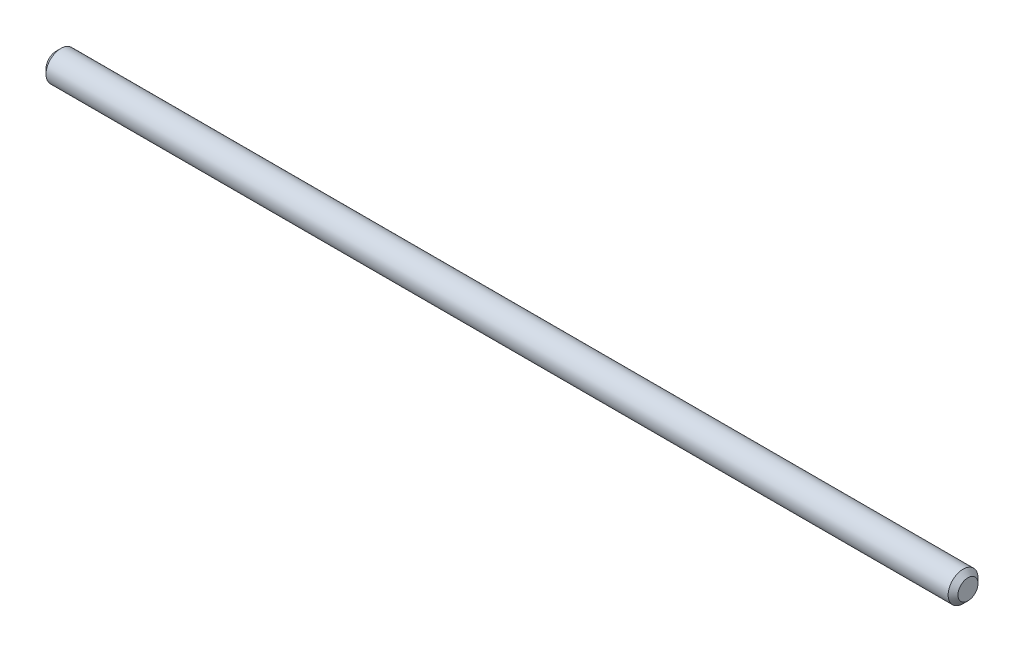
SolidWorks part; units mm, degrees
material "Plain Carbon Steel"
ref_plane "Front Plane" through (0, 0, 0) normal (0, 0, 1) x (1, 0, 0)
ref_plane "Top Plane" through (0, 0, 0) normal (0, 1, 0) x (1, 0, 0)
ref_plane "Right Plane" through (0, 0, 0) normal (1, 0, 0) x (0, 0, -1)
sketch "Sketch1" plane through (0, 0, 0) normal (0, 0, 1) x (1, 0, 0)
  line L0 (-73.66, 0) -> (73.66, 0) construction
  line L1 (73.66, 2.413) -> (73.66, -2.413) construction
  line L2 (-73.66, 2.413) -> (-73.66, -2.413) construction
  line L3 (73.66, 2.413) -> (4.8683, 2.413) construction
  point P6 (69.9558, -2.413)
  point P9 (-64.008, 0)
  point P10 (64.008, 0)
  point P11 (-38.608, 0)
  point P12 (38.608, 0)
  dimension "D1" = 3.7042
  dimension "D2" = 9.652
  dimension "D3" = 9.652
  dimension "D4" = 25.4
  dimension "D5" = 25.4
sketch "Sketch2" plane through (0, 0, 0) normal (1, 0, 0) x (0, 0, -1)
  circle A0 centre (0, 0) radius 2.413
extrude "Boss-Extrude1" add sketch "Sketch2" against normal up to vertex (73.66 mm away) and the other way up to vertex (73.66 mm away) up to point (-73.66, 0, 0) other way up to point (73.66, 0, 0)
chamfer "Chamfer1" distance 0.7938 angle 45 2 edges at (-73.66, 0, -2.413) (73.66, 0, -2.413)
sketch "Drawing1" plane through (0, 0, 0) normal (1, 0, 0) x (0, 0, -1)
  circle A0 centre (0, 0) radius 2.413
sketch "Sketch3" [suppressed] plane through (152.4, 0, 0) normal (1, 0, 0) x (0, 0, -1)
  circle A1 centre (0, 0) radius 2.413
  circle A2 centre (0, 0) radius 2.413
  dimension "D1" = 0
curve "Helix/Spiral1" [suppressed] pitch 1.0583 height 69.85 turns 66 parameters "Pitch"=1.0583
sketch "Sketch4" [suppressed] plane through (0, 0, 0) normal (0, 0, 1) x (1, 0, 0)
  line L0 (152.863, 1.7256) -> (152.863, 2.413) construction
  line L1 (152.5984, 2.0693) -> (153.1276, 2.0693) construction
  line L2 (152.0031, 3.1004) -> (152.7969, 1.7256)
  line L3 (153.7229, 3.1004) -> (152.9292, 1.7256)
  line L4 (152.0031, 3.1004) -> (153.7229, 3.1004)
  line L5 (152.7969, 1.7256) -> (152.9292, 1.7256) construction
  line L7 (152.7969, 1.7256) -> (152.4, 2.413) construction
  line L8 (152.7969, 1.7256) -> (152.9292, 1.7256)
  line L9 (152.4, 2.413) -> (153.326, 2.413) construction
  line L10 (153.326, 2.413) -> (152.9292, 1.7256) construction
  point P9 (152.4, 2.413)
  point P11 (153.326, 2.413)
  dimension "D2" = 0.1323
  dimension "D1" = 0.5292
  dimension "D3" = 60
sweep "Cut-Sweep3" [suppressed] cut profiles "Sketch4" path "Helix/Spiral1"
pattern_linear "LPattern1" [suppressed] count 3 spacing 67.7333 along (-1, 0, 0) of bodies 102
ref_plane "Plane1" [suppressed] through (-117.348, 0, 0) normal (1, 0, 0) x (0, 0, -1)
ref_plane "Plane2" [suppressed] through (117.348, 0, 0) normal (1, 0, 0) x (0, 0, -1)
split "Split1" [suppressed] bodies to split 103
equation "\"D3@Helix/Spiral1\"=\"Pitch@Helix/Spiral1\"+\"Segment Length@Sketch1\""
equation "\"D1@Chamfer1\" = \"Pitch@Helix/Spiral1\"*.75"
equation "\"D2@Sketch4\"=\"Pitch@Helix/Spiral1\"*.125"
equation "\"D1@Sketch1\" = \"Pitch@Helix/Spiral1\"*3.50"
equation "\"Segment Length@Sketch1\" = \"Pitch@Helix/Spiral1\"*65"
equation "\"D1@LPattern1\"=(\"Length@Sketch1\"/(\"Segment Length@Sketch1\"-\"Pitch@Helix/Spiral1\"))+1"
equation "\"D3@LPattern1\"=\"Segment Length@Sketch1\"-\"Pitch@Helix/Spiral1\""
equation "\"D2@Sketch1\"=\"Thread Diameter@Sketch1\"*2"
equation "\"D3@Sketch1\"=\"Thread Diameter@Sketch1\"*2"
equation "\"D1@Sketch4\"=\"Pitch@Helix/Spiral1\"*.5"
